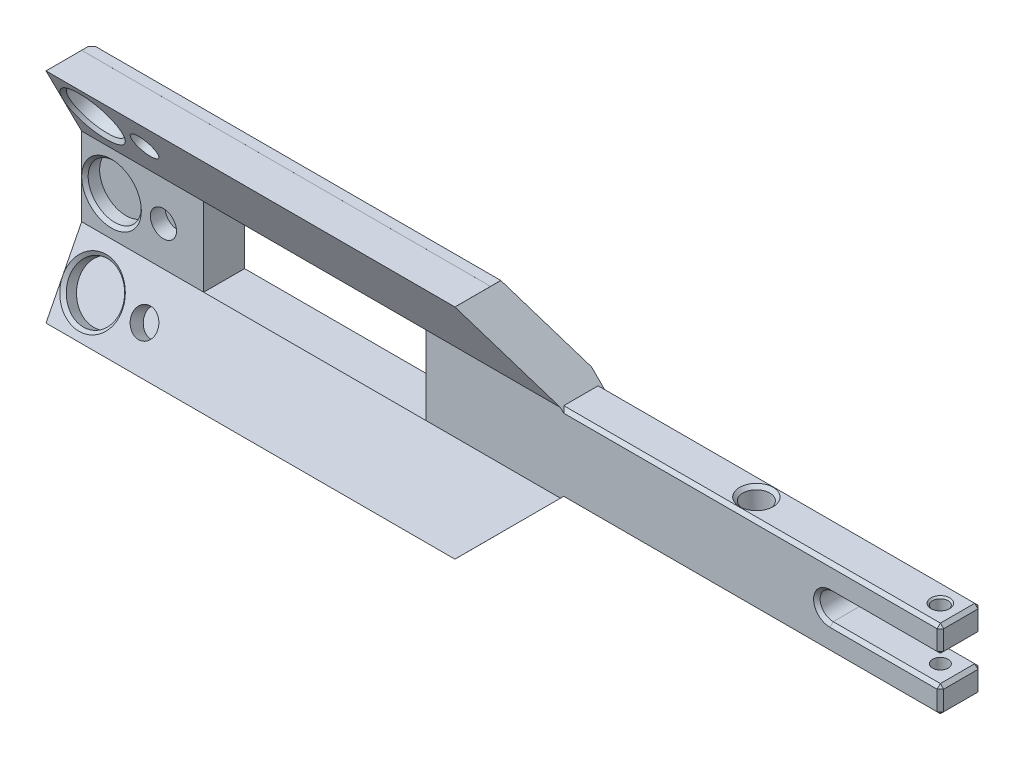
SolidWorks part; units mm, degrees
ref_plane "Front" through (0, 0, 0) normal (0, 0, 1) x (1, 0, 0)
ref_plane "Top" through (0, 0, 0) normal (0, 1, 0) x (1, 0, 0)
ref_plane "Right" through (0, 0, 0) normal (1, 0, 0) x (0, 0, -1)
sketch "Sketch1" plane through (0, 0, 0) normal (0, 0, 1) x (1, 0, 0)
  line L1 (52.5, -4.8) -> (-52.5, -4.8)
  line L2 (52.5, -4.8) -> (52.5, 4.8)
  line L3 (52.5, 4.8) -> (-52.5, 4.8)
  line L4 (-52.5, -4.8) -> (-52.5, 4.8)
  line L5 (52.5, -4.8) -> (-52.5, 4.8) construction
  line L6 (52.5, 4.8) -> (-52.5, -4.8) construction
  point P0 (0, 0)
  dimension "D1" = 9.6
  dimension "D2" = 105
extrude "Boss-Extrude1" add sketch "Sketch1" along normal blind 5
sketch "Sketch2" plane through (0, 4.8, 0) normal (0, 1, 0) x (1, 0, 0)
  line L0 (52.5, -5) -> (52.5, 0) construction
  line L2 (52.5, 0) -> (-52.5, 0) construction
  circle A0 centre (27.5, -2.5) radius 1.65
  dimension "D3" = 3.3
  dimension "D1" = 2.5
  dimension "D2" = 25
sketch "Sketch4" plane through (0, 0, 5) normal (0, 0, 1) x (1, 0, 0)
  line L0 (39, 0) -> (45, 0) construction
  line L1 (39, 1.6) -> (45, 1.6)
  line L2 (39, -1.6) -> (45, -1.6)
  arc A0 (39, 1.6) -> (39, -1.6) centre (39, 0) ccw
  arc A1 (45, -1.6) -> (45, 1.6) centre (45, 0) ccw
  point P2 (42, 0)
  dimension "D1" = 1.6
  dimension "D2" = 42
  dimension "D3" = 6
extrude "Cut-Extrude1" cut sketch "Sketch4" against normal blind 5
sketch "Sketch14" plane through (0, 0, 5) normal (0, 0, 1) x (1, 0, 0)
  line L0 (39, -1.6) -> (45, -1.6) construction
  line L1 (44.5, -1.6) -> (52.5, -1.6)
  line L2 (44.5, -1.6) -> (44.5, 1.6)
  line L3 (44.5, 1.6) -> (52.5, 1.6)
  line L4 (52.5, -1.6) -> (52.5, 1.6)
  line L5 (52.5, -4.8) -> (52.5, 4.8) construction
  line L6 (45, 1.6) -> (39, 1.6) construction
  dimension "D1" = 8
extrude "Cut-Extrude7" cut sketch "Sketch14" against normal blind 10
sketch "Sketch8" plane through (0, 0, 0) normal (0, 0, -1) x (-1, 0, 0)
  line L0 (52.5, 4.8) -> (52.5, -4.8) construction
  line L1 (52.5, 13.355) -> (2.5, 13.355)
  line L2 (52.5, 13.355) -> (52.5, -13.355)
  line L3 (52.5, -13.355) -> (2.5, -13.355)
  line L4 (2.5, 13.355) -> (2.5, -13.355)
  line L5 (2.5, 0) -> (52.5, 0) construction
  line L7 (-52.5, 0) -> (53.7381, 0) construction
  dimension "D1" = 26.71
  dimension "D3" = 50
extrude "Boss-Extrude3" add sketch "Sketch8" against normal up to surface (5 mm away) up to face at (22.675, 0, 5)
sketch "Sketch9" plane through (-52.5, 0, 0) normal (-1, 0, 0) x (0, 0, 1)
  line L0 (5, 13.355) -> (5, -13.355) construction
  line L1 (5, 13.3543) -> (9.357, 13.3543)
  line L2 (9.357, 13.3543) -> (5, 4.8)
  line L3 (5, 4.8) -> (5, 13.3543)
  line L4 (-3.9634, 0) -> (12.9509, 0) construction
  line L5 (9.357, -13.3543) -> (5, -4.8)
  line L6 (5, -13.3543) -> (9.357, -13.3543)
  line L7 (5, -4.8) -> (5, -13.3543)
  circle A0 centre (25, 0) radius 20 construction
  dimension "D1" = 40
  dimension "D2" = 9.6
  dimension "D3" = 9.6
extrude "Boss-Extrude4" add sketch "Sketch9" against normal up to surface (50 mm away) up to face at (-2.5, 9.0775, 2.5)
sketch "Sketch13" plane through (-52.5, 0, 0) normal (-1, 0, 0) x (0, 0, 1)
  line L0 (0, 6) -> (3.7462, 13.355)
  line L1 (0, 13.355) -> (0, -13.355) construction
  line L2 (5, 13.355) -> (0, 13.355) construction
  line L3 (3.7462, 13.355) -> (-2, 13.355)
  line L4 (-2, 13.355) -> (-2, -13.355)
  line L5 (-2, -13.355) -> (3.7462, -13.355)
  line L6 (5, -13.355) -> (0, -13.355) construction
  line L7 (3.7462, -13.355) -> (0, -6)
  line L8 (0, -6) -> (0, 6)
  line L10 (5, 4.8) -> (9.357, 13.3543) construction
  line L11 (9.357, -13.3543) -> (5, -4.8) construction
  dimension "D1" = 5
  dimension "D2" = 5
  dimension "D3" = 2
extrude "Cut-Extrude6" cut sketch "Sketch13" against normal through all
chamfer "Chamfer4" distance 8.55 2 edges at (-2.5, 4.8, 2.5) (-2.5, -4.8, 2.5)
sketch "Sketch10" plane through (-52.5, 0, 0) normal (-1, 0, 0) x (0, 0, 1)
  line L0 (5, 4.8) -> (5, -4.8) construction
  line L1 (5, 4.8) -> (9.357, 13.3543) construction
  line L2 (9.357, -13.3543) -> (5, -4.8) construction
  circle A0 centre (25, 0) radius 20
sketch "Sketch11" plane through (0, 0, 5) normal (0, 0, 1) x (1, 0, 0)
  line L2 (-52.5, 4.8) -> (-52.5, -4.8) construction
  circle A0 centre (-48.85, 0) radius 3.25
  circle A1 centre (-42.5, 0) radius 1.6
  dimension "D1" = 6.5
  dimension "D3" = 10
  dimension "D2" = 3.65
extrude "Cut-Extrude3" cut sketch "Sketch11" against normal blind 1.8
sketch "Sketch12" plane through (0, -1.0334, 2.0288) normal (0, -0.4539, 0.8911) x (1, 0, 0)
  line L0 (-52.5, 6.5464) -> (-52.5, 16.1464) construction
  line L1 (-2.5, 16.1464) -> (-52.5, 16.1464) construction
  line L2 (-52.5, 31.3464) -> (-52.5, -8.6536) construction
  circle A0 centre (-48.85, 11.6464) radius 3.25
  circle A1 centre (-42.5, 11.6464) radius 1.6
  dimension "D1" = 6.5
  dimension "D4" = 10
  dimension "D2" = 4.5
  dimension "D3" = 3.65
extrude "Cut-Extrude4" cut sketch "Sketch12" against normal blind 1.8
mirror "Mirror2" about plane through (0, 0, 0) normal (0, 1, 0) of "Cut-Extrude4"
chamfer "Chamfer2" distance 0.4 angle 45 3 edges at (-45.6, 0, 5) (-48.85, -6.4485, 5.8396) (-48.85, 6.4485, 5.8396)
ref_plane "Plane1" through (-48.5, 0, 0) normal (-1, 0, 0) x (0, 0, 1)
extrude "Cut-Extrude5" cut sketch "Sketch2" against normal blind 10
chamfer "Chamfer5" distance 0.4 angle 45 20 edges at (25.85, -4.8, 2.5) (25.85, 4.8, 2.5) (52.5, 4.8, 2.5) (29.275, 4.8, 5) (52.5, -3.2, 5) (52.5, 3.2, 5) (29.275, -4.8, 5) (52.5, -4.8, 2.5) (29.275, 4.8, 0) (29.275, -4.8, 0) (52.5, 3.2, 0) (52.5, -3.2, 0) (45.75, -1.6, 0) (37.4, 0, 0) (45.75, 1.6, 0) (45.75, 1.6, 5) (37.4, 0, 5) (45.75, -1.6, 5) (52.5, 1.6, 2.5) (52.5, -1.6, 2.5)
chamfer "Chamfer6" distance 0.4 angle 45 3 edges at (-52.5, 9.6775, 1.8731) (-52.5, -9.6775, 1.8731) (-52.5, 0, 0)
sketch "Sketch15" plane through (0, -4.8, 0) normal (0, -1, 0) x (1, 0, 0)
  line L0 (52.5, 4.6) -> (52.5, 0.4) construction
  line L1 (52.1, 0) -> (6.45, 0) construction
  circle A0 centre (50, 2.5) radius 0.95
  dimension "D1" = 1.9
  dimension "D2" = 2.5
  dimension "D3" = 2.5
extrude "Cut-Extrude8" cut sketch "Sketch15" against normal blind 10
chamfer "Chamfer11" distance 0.2 angle 45 2 edges at (50.95, 4.8, 2.5) (50.95, -4.8, 2.5)
sketch "Sketch16" plane through (0, 0, 5) normal (0, 0, 1) x (1, 0, 0)
  line L1 (-10.4, 4.8) -> (-37.5733, 4.8)
  line L3 (-37.5733, -4.8) -> (-10.4, -4.8)
  line L7 (6.05, 4.8) -> (-52.5, 4.8) construction
  line L8 (6.05, -4.8) -> (-52.5, -4.8) construction
  line L11 (-37.5733, 4.8) -> (-37.5733, -4.8)
  line L12 (-10.4, 4.8) -> (-10.4, -4.8)
extrude "Cut-Extrude9" cut sketch "Sketch16" against normal blind 10
sketch "Sketch17" plane through (0, 0, 0) normal (0, 0, 1) x (1, 0, 0)
  line L13 (29.15, -4.4) -> (29.15, 4.4) construction
  circle A0 centre (-2.5, -0.2) radius 1.6
  dimension "D1" = 31.65
extrude "Cut-Extrude10" cut sketch "Sketch17" against normal mid plane 8
